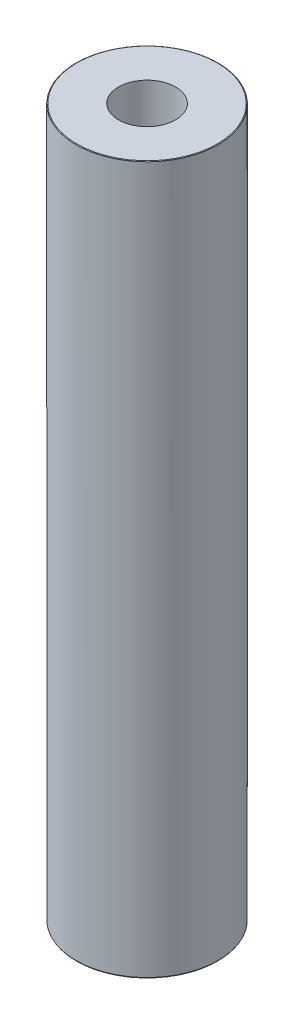
SolidWorks part; units mm, degrees
ref_plane "Front Plane" through (0, 0, 0) normal (0, 0, 1) x (1, 0, 0)
ref_plane "Top Plane" through (0, 0, 0) normal (0, 1, 0) x (1, 0, 0)
ref_plane "Right Plane" through (0, 0, 0) normal (1, 0, 0) x (0, 0, -1)
sketch "Sketch1" plane through (0, 0, 0) normal (0, 1, 0) x (1, 0, 0)
  circle A0 centre (0, 0) radius 47.5
  dimension "SHAFT_OD" = 95
extrude "Boss-Extrude1" add sketch "Sketch1" along normal blind 473.5571
sketch "Sketch2" plane through (0, 0, 0) normal (0, 1, 0) x (1, 0, 0)
  circle A0 centre (0, 0) radius 19.094
  dimension "BORE_D" = 38.188
extrude "Cut-Extrude1" cut sketch "Sketch2" along normal through all
chamfer "Chamfer1" distance 0.2816 angle 60 2 edges at (0, 473.5571, 47.5) (0, 0, 47.5) first distance on face at (0, 473.5571, 47.5) first distance on face at (0, 0, 19.094)
